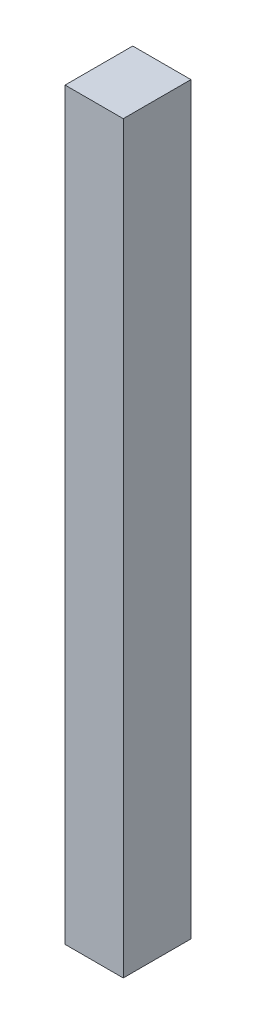
SolidWorks part; units mm, degrees
ref_plane "Front Plane" through (0, 0, 0) normal (0, 0, 1) x (1, 0, 0)
ref_plane "Top Plane" through (0, 0, 0) normal (0, 1, 0) x (1, 0, 0)
ref_plane "Right Plane" through (0, 0, 0) normal (1, 0, 0) x (0, 0, -1)
sketch "Sketch1" plane through (0, 0, 0) normal (0, 1, 0) x (1, 0, 0)
  line L1 (0, 0) -> (25.4, 0)
  line L2 (0, 0) -> (0, 50.8)
  line L3 (0, 50.8) -> (25.4, 50.8)
  line L4 (25.4, 0) -> (25.4, 50.8)
  dimension "D1" = 25.4
  dimension "D2" = 50.8
extrude "Boss-Extrude1" add sketch "Sketch1" along normal blind 558.8
sketch "Sketch2" plane through (0, 0, -50.8) normal (0, 0, -1) x (-1, 0, 0)
  line L0 (-25.4, 558.8) -> (0, 558.8) construction
  line L1 (-25.4, 558.8) -> (-25.4, 0) construction
  circle A0 centre (-12.7, 546.1) radius 6.35
  dimension "D1" = 12.7
  dimension "D2" = 12.7
extrude "Boss-Extrude2" add sketch "Sketch2" along normal blind 6.35
sketch "Sketch3" plane through (0, 0, 0) normal (-1, 0, 0) x (0, 0, 1)
  line L1 (0, 0) -> (-50.8, 0)
  line L2 (0, 0) -> (0, 558.8)
  line L3 (0, 558.8) -> (-50.8, 558.8)
  line L4 (-50.8, 0) -> (-50.8, 558.8)
extrude "Boss-Extrude3" add sketch "Sketch3" along normal blind 18.288
